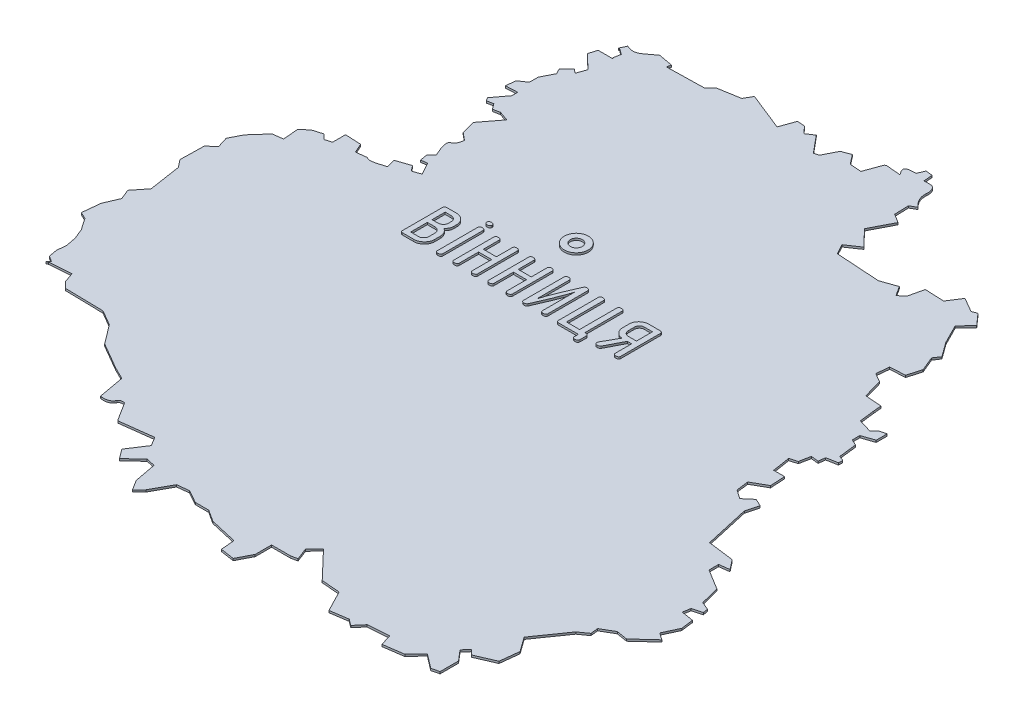
SolidWorks part; units mm, degrees
ref_plane "Спереди" through (0, 0, 0) normal (0, 0, 1) x (1, 0, 0)
ref_plane "Сверху" through (0, 0, 0) normal (0, 1, 0) x (1, 0, 0)
ref_plane "Справа" through (0, 0, 0) normal (1, 0, 0) x (0, 0, -1)
sketch "Эскиз1" plane through (0, 0, 0) normal (0, 1, 0) x (1, 0, 0)
  line B0 (-2034.573, 5821.9238) -> (-2000.1789, 5816.7524)
  line B1 (-2000.1789, 5816.7524) -> (-1981.3651, 5853.0846)
  line B2 (-1981.3651, 5853.0846) -> (-1981.3651, 5893.976)
  line B3 (-1981.3651, 5893.976) -> (-1933.9789, 5893.976)
  line B4 (-1933.9789, 5893.976) -> (-1918.4036, 5897.2145)
  line B5 (-1918.4036, 5897.2145) -> (-1930.0952, 5927.692)
  line B6 (-1930.0952, 5927.692) -> (-1908.0353, 5950.4326)
  line B7 (-1908.0353, 5950.4326) -> (-1841.1927, 5880.3337)
  line B8 (-1841.1927, 5880.3337) -> (-1795.1272, 5876.4576)
  line B9 (-1795.1272, 5876.4576) -> (-1767.8679, 5823.8847)
  line B10 (-1767.8679, 5823.8847) -> (-1723.7253, 5830.3947)
  line B11 (-1723.7253, 5830.3947) -> (-1708.1779, 5818.6955)
  line B12 (-1708.1779, 5818.6955) -> (-1689.3413, 5840.7732)
  line B13 (-1689.3413, 5840.7732) -> (-1636.7862, 5844.6391)
  line B14 (-1636.7862, 5844.6391) -> (-1628.333, 5816.7524)
  line B15 (-1628.333, 5816.7524) -> (-1578.3789, 5823.8847)
  line B16 (-1578.3789, 5823.8847) -> (-1551.1145, 5853.0846)
  line B17 (-1551.1145, 5853.0846) -> (-1515.4123, 5825.8177)
  line B18 (-1515.4123, 5825.8177) -> (-1496.5934, 5830.3947)
  line B19 (-1496.5934, 5830.3947) -> (-1496.5934, 5876.4576)
  line B20 (-1496.5934, 5876.4576) -> (-1518.6787, 5902.4114)
  line B21 (-1518.6787, 5902.4114) -> (-1505.0414, 5917.9968)
  line B22 (-1505.0414, 5917.9968) -> (-1493.36, 5905.6397)
  line B23 (-1493.36, 5905.6397) -> (-1445.3362, 5926.4499)
  line B24 (-1445.3362, 5926.4499) -> (-1440.1444, 5973.7803)
  line B25 (-1440.1444, 5973.7803) -> (-1466.0982, 6010.1302)
  line B26 (-1466.0982, 6010.1302) -> (-1412.8953, 6086.0381)
  line B27 (-1412.8953, 6086.0381) -> (-1390.8456, 6101.6236)
  line B28 (-1390.8456, 6101.6236) -> (-1392.776, 6120.4627)
  line B29 (-1392.776, 6120.4627) -> (-1361.628, 6138.611)
  line B30 (-1361.628, 6138.611) -> (-1334.3788, 6134.067)
  line B31 (-1334.3788, 6134.067) -> (-1288.2956, 6176.2488)
  line B32 (-1288.2956, 6176.2488) -> (-1305.814, 6188.5728)
  line B33 (-1305.814, 6188.5728) -> (-1288.2956, 6226.1928)
  line B34 (-1288.2956, 6226.1928) -> (-1292.2148, 6256.7363)
  line B35 (-1292.2148, 6256.7363) -> (-1322.6948, 6261.9077)
  line B36 (-1322.6948, 6261.9077) -> (-1319.4563, 6280.7393)
  line B37 (-1319.4563, 6280.7393) -> (-1295.4356, 6287.2264)
  line B38 (-1295.4356, 6287.2264) -> (-1297.3736, 6299.5556)
  line B39 (-1297.3736, 6299.5556) -> (-1317.4904, 6307.9782)
  line B40 (-1317.4904, 6307.9782) -> (-1329.8297, 6355.3543)
  line B41 (-1329.8297, 6355.3543) -> (-1380.4392, 6386.5023)
  line B42 (-1380.4392, 6386.5023) -> (-1380.4392, 6410.518)
  line B43 (-1380.4392, 6410.518) -> (-1355.123, 6413.7718)
  line B44 (-1355.123, 6413.7718) -> (-1373.9571, 6437.7722)
  line B45 (-1373.9571, 6437.7722) -> (-1438.8516, 6446.2127)
  line B46 (-1438.8516, 6446.2127) -> (-1464.1601, 6558.468)
  line B47 (-1464.1601, 6558.468) -> (-1455.7096, 6589.6109)
  line B48 (-1455.7096, 6589.6109) -> (-1474.5487, 6598.0767)
  line B49 (-1474.5487, 6598.0767) -> (-1496.5934, 6579.2452)
  line B50 (-1496.5934, 6579.2452) -> (-1518.6787, 6594.8128)
  line B51 (-1518.6787, 6594.8128) -> (-1522.5547, 6625.3131)
  line B52 (-1522.5547, 6625.3131) -> (-1486.215, 6646.0776)
  line B53 (-1486.215, 6646.0776) -> (-1488.1885, 6683.0677)
  line B54 (-1488.1885, 6683.0677) -> (-1515.4123, 6683.0677)
  line B55 (-1515.4123, 6683.0677) -> (-1522.5547, 6727.8377)
  line B56 (-1522.5547, 6727.8377) -> (-1503.741, 6733.0269)
  line B57 (-1503.741, 6733.0269) -> (-1498.5492, 6760.2938)
  line B58 (-1498.5492, 6760.2938) -> (-1479.7303, 6758.3507)
  line B59 (-1479.7303, 6758.3507) -> (-1477.7974, 6775.2189)
  line B60 (-1477.7974, 6775.2189) -> (-1450.533, 6780.4157)
  line B61 (-1450.533, 6780.4157) -> (-1450.533, 6790.8119)
  line B62 (-1450.533, 6790.8119) -> (-1462.8597, 6795.9884)
  line B63 (-1462.8597, 6795.9884) -> (-1468.0438, 6840.126)
  line B64 (-1468.0438, 6840.126) -> (-1482.9942, 6847.2583)
  line B65 (-1482.9942, 6847.2583) -> (-1482.9942, 6866.0874)
  line B66 (-1482.9942, 6866.0874) -> (-1452.4761, 6876.448)
  line B67 (-1452.4761, 6876.448) -> (-1452.4761, 6903.6971)
  line B68 (-1452.4761, 6903.6971) -> (-1468.0438, 6899.8084)
  line B69 (-1468.0438, 6899.8084) -> (-1479.7303, 6888.1269)
  line B70 (-1479.7303, 6888.1269) -> (-1514.1372, 6898.5181)
  line B71 (-1514.1372, 6898.5181) -> (-1518.6787, 6936.1634)
  line B72 (-1518.6787, 6936.1634) -> (-1520.6091, 6956.2675)
  line B73 (-1520.6091, 6956.2675) -> (-1561.5031, 6959.5136)
  line B74 (-1561.5031, 6959.5136) -> (-1575.1251, 7007.5501)
  line B75 (-1575.1251, 7007.5501) -> (-1597.2028, 7019.8717)
  line B76 (-1597.2028, 7019.8717) -> (-1593.9516, 7051.6623)
  line B77 (-1593.9516, 7051.6623) -> (-1556.3113, 7053.613)
  line B78 (-1556.3113, 7053.613) -> (-1546.5704, 7088.0021)
  line B79 (-1546.5704, 7088.0021) -> (-1561.5031, 7123.6992)
  line B80 (-1561.5031, 7123.6992) -> (-1551.1145, 7139.2669)
  line B81 (-1551.1145, 7139.2669) -> (-1577.0657, 7174.9564)
  line B82 (-1577.0657, 7174.9564) -> (-1601.0712, 7222.3401)
  line B83 (-1601.0712, 7222.3401) -> (-1575.1251, 7250.2446)
  line B84 (-1575.1251, 7250.2446) -> (-1599.7936, 7278.1643)
  line B85 (-1599.7936, 7278.1643) -> (-1612.7654, 7273.5973)
  line B86 (-1612.7654, 7273.5973) -> (-1648.4549, 7294.3618)
  line B87 (-1648.4549, 7294.3618) -> (-1669.2093, 7261.9235)
  line B88 (-1669.2093, 7261.9235) -> (-1717.233, 7263.8742)
  line B89 (-1717.233, 7263.8742) -> (-1725.6811, 7227.5294)
  line B90 (-1725.6811, 7227.5294) -> (-1740.601, 7213.9048)
  line B91 (-1740.601, 7213.9048) -> (-1756.1814, 7237.9129)
  line B92 (-1756.1814, 7237.9129) -> (-1795.1272, 7224.2756)
  line B93 (-1795.1272, 7224.2756) -> (-1904.7892, 7231.4283)
  line B94 (-1904.7892, 7231.4283) -> (-1918.4036, 7256.7317)
  line B95 (-1918.4036, 7256.7317) -> (-1885.9602, 7278.7993)
  line B96 (-1885.9602, 7278.7993) -> (-1924.9111, 7319.6907)
  line B97 (-1924.9111, 7319.6907) -> (-1896.3615, 7374.8443)
  line B98 (-1896.3615, 7374.8443) -> (-1918.4036, 7388.4663)
  line B99 (-1918.4036, 7388.4663) -> (-1919.7066, 7424.1635)
  line B100 (-1919.7066, 7424.1635) -> (-1904.7892, 7432.5886)
  line B101 (-1935.2844, 7497.4933) -> (-1954.1109, 7497.4933)
  line B102 (-1954.1109, 7497.4933) -> (-1956.0591, 7519.5582)
  line B103 (-1956.0591, 7519.5582) -> (-1972.9374, 7521.4963)
  line B104 (-1972.9374, 7521.4963) -> (-1980.0646, 7503.9855)
  line B105 (-1980.0646, 7503.9855) -> (-1996.9277, 7502.6774)
  line B106 (-1996.9277, 7480.6048) -> (-2034.573, 7483.8687)
  line B107 (-2034.573, 7483.8687) -> (-2037.809, 7481.9154)
  line B108 (-2037.809, 7481.9154) -> (-2053.3944, 7439.0834)
  line B109 (-2053.3944, 7439.0834) -> (-2081.9593, 7441.0341)
  line B110 (-2081.9593, 7441.0341) -> (-2100.7476, 7465.0321)
  line B111 (-2100.7476, 7465.0321) -> (-2122.8253, 7456.6018)
  line B112 (-2122.8253, 7456.6018) -> (-2140.3615, 7422.2153)
  line B113 (-2140.3615, 7422.2153) -> (-2152.0353, 7418.9692)
  line B114 (-2152.0353, 7418.9692) -> (-2187.7274, 7461.791)
  line B115 (-2187.7274, 7461.791) -> (-2206.5539, 7449.4568)
  line B116 (-2206.5539, 7449.4568) -> (-2222.1215, 7466.9879)
  line B117 (-2222.1215, 7466.9879) -> (-2240.9302, 7468.2833)
  line B118 (-2240.9302, 7468.2833) -> (-2254.57, 7430.6481)
  line B119 (-2254.57, 7430.6481) -> (-2348.6491, 7468.2833)
  line B120 (-2348.6491, 7468.2833) -> (-2360.3407, 7448.1792)
  line B121 (-2360.3407, 7448.1792) -> (-2413.5486, 7439.0834)
  line B122 (-2413.5486, 7439.0834) -> (-2430.4193, 7424.1635)
  line B123 (-2430.4193, 7424.1635) -> (-2522.568, 7422.2153)
  line B124 (-2522.568, 7422.2153) -> (-2520.63, 7432.5886)
  line B125 (-2520.63, 7432.5886) -> (-2556.3271, 7439.0834)
  line B126 (-2616.0247, 7418.9692) -> (-2623.152, 7403.399)
  line B127 (-2623.152, 7403.399) -> (-2622.5195, 7404.6918)
  line B128 (-2622.5195, 7404.6918) -> (-2606.2788, 7393.0027)
  line B129 (-2606.2788, 7393.0027) -> (-2609.5477, 7374.8443)
  line B130 (-2609.5477, 7374.8443) -> (-2606.2788, 7372.8936)
  line B131 (-2606.2788, 7372.8936) -> (-2643.9241, 7372.8936)
  line B132 (-2643.9241, 7372.8936) -> (-2650.4036, 7352.1214)
  line B133 (-2650.4036, 7352.1214) -> (-2614.7192, 7318.3699)
  line B134 (-2614.7192, 7318.3699) -> (-2623.152, 7294.3618)
  line B135 (-2623.152, 7294.3618) -> (-2633.5558, 7302.8099)
  line B136 (-2633.5558, 7302.8099) -> (-2652.3696, 7283.9885)
  line B137 (-2652.3696, 7283.9885) -> (-2645.2297, 7270.3512)
  line B138 (-2645.2297, 7270.3512) -> (-2660.7999, 7239.856)
  line B139 (-2660.7999, 7239.856) -> (-2660.7999, 7217.8037)
  line B140 (-2660.7999, 7217.8037) -> (-2680.9167, 7204.1842)
  line B141 (-2680.9167, 7204.1842) -> (-2682.8547, 7180.166)
  line B142 (-2682.8547, 7180.166) -> (-2653.665, 7181.4665)
  line B143 (-2653.665, 7181.4665) -> (-2653.665, 7166.5109)
  line B144 (-2653.665, 7166.5109) -> (-2679.6187, 7132.1447)
  line B145 (-2679.6187, 7132.1447) -> (-2674.4117, 7123.6992)
  line B146 (-2674.4117, 7123.6992) -> (-2658.8491, 7126.9606)
  line B147 (-2658.8491, 7126.9606) -> (-2648.4707, 7113.3233)
  line B148 (-2648.4707, 7113.3233) -> (-2631.5899, 7116.5593)
  line B149 (-2631.5899, 7116.5593) -> (-2607.5843, 7108.1163)
  line B150 (-2607.5843, 7108.1163) -> (-2643.9241, 7060.753)
  line B151 (-2643.9241, 7060.753) -> (-2634.8233, 7026.3588)
  line B152 (-2634.8233, 7026.3588) -> (-2616.0247, 7010.7886)
  line B153 (-2619.9211, 6944.5886) -> (-2631.5899, 6932.2645)
  line B154 (-2631.5899, 6932.2645) -> (-2628.3564, 6913.4609)
  line B155 (-2628.3564, 6913.4609) -> (-2612.7862, 6915.3989)
  line B156 (-2612.7862, 6915.3989) -> (-2595.9105, 6884.8834)
  line B157 (-2595.9105, 6884.8834) -> (-2616.0247, 6877.7612)
  line B158 (-2616.0247, 6877.7612) -> (-2626.4057, 6891.3807)
  line B159 (-2626.4057, 6891.3807) -> (-2660.7999, 6879.7094)
  line B160 (-2660.7999, 6879.7094) -> (-2655.6106, 6857.6317)
  line B161 (-2699.7406, 6852.4374) -> (-2726.9897, 6849.1913)
  line B162 (-2726.9897, 6849.1913) -> (-2737.3682, 6872.5694)
  line B163 (-2737.3682, 6872.5694) -> (-2776.9642, 6874.5151)
  line B164 (-2776.9642, 6874.5151) -> (-2776.9642, 6842.0691)
  line B165 (-2776.9642, 6842.0691) -> (-2793.8298, 6836.8697)
  line B166 (-2793.8298, 6836.8697) -> (-2805.5087, 6849.1913)
  line B167 (-2805.5087, 6849.1913) -> (-2829.5143, 6842.0691)
  line B168 (-2829.5143, 6842.0691) -> (-2848.3509, 6826.4913)
  line B169 (-2848.3509, 6826.4913) -> (-2845.0921, 6787.5607)
  line B170 (-2845.0921, 6787.5607) -> (-2870.4057, 6784.307)
  line B171 (-2870.4057, 6784.307) -> (-2902.8441, 6747.9596)
  line B172 (-2902.8441, 6747.9596) -> (-2918.4244, 6717.4745)
  line B173 (-2918.4244, 6717.4745) -> (-2909.984, 6690.2076)
  line B174 (-2909.984, 6690.2076) -> (-2928.808, 6673.3445)
  line B175 (-2928.808, 6673.3445) -> (-2930.1161, 6613.6444)
  line B176 (-2930.1161, 6613.6444) -> (-2915.1732, 6594.8128)
  line B177 (-2915.1732, 6594.8128) -> (-2902.8441, 6514.3431)
  line B178 (-2902.8441, 6514.3431) -> (-2928.808, 6481.8971)
  line B179 (-2928.808, 6481.8971) -> (-2918.4244, 6456.5987)
  line B180 (-2918.4244, 6456.5987) -> (-2934.0048, 6420.2437)
  line B181 (-2934.0048, 6420.2437) -> (-2938.5514, 6375.4813)
  line B182 (-2938.5514, 6375.4813) -> (-2921.6629, 6367.7063)
  line B183 (-2921.6629, 6367.7063) -> (-2901.5487, 6338.4786)
  line B184 (-2901.5487, 6338.4786) -> (-2891.1652, 6313.203)
  line B185 (-2891.1652, 6313.203) -> (-2885.9912, 6287.2264)
  line B186 (-2885.9912, 6287.2264) -> (-2887.9343, 6261.9077)
  line B187 (-2887.9343, 6261.9077) -> (-2884.0176, 6241.1559)
  line B188 (-2884.0176, 6241.1559) -> (-2870.4057, 6232.7206)
  line B189 (-2870.4057, 6232.7206) -> (-2876.8853, 6225.601)
  line B190 (-2876.8853, 6225.601) -> (-2872.3539, 6227.5263)
  line B191 (-2872.3539, 6227.5263) -> (-2817.8404, 6231.4074)
  line B192 (-2817.8404, 6231.4074) -> (-2809.4051, 6207.4044)
  line B193 (-2809.4051, 6207.4044) -> (-2793.8298, 6191.824)
  line B194 (-2793.8298, 6191.824) -> (-2698.4325, 6189.8733)
  line B195 (-2698.4325, 6189.8733) -> (-2660.7999, 6167.821)
  line B196 (-2660.7999, 6167.821) -> (-2625.1205, 6120.4627)
  line B197 (-2625.1205, 6120.4627) -> (-2560.2184, 6082.8098)
  line B198 (-2560.2184, 6082.8098) -> (-2529.0729, 6067.2421)
  line B199 (-2442.0982, 5970.524) -> (-2360.3407, 5980.9304)
  line B200 (-2360.3407, 5980.9304) -> (-2346.7085, 5958.8705)
  line B201 (-2346.7085, 5958.8705) -> (-2375.9185, 5914.103)
  line B202 (-2375.9185, 5914.103) -> (-2358.3951, 5890.7477)
  line B203 (-2358.3951, 5890.7477) -> (-2322.7005, 5924.4636)
  line B204 (-2322.7005, 5924.4636) -> (-2300.6456, 5919.2744)
  line B205 (-2300.6456, 5919.2744) -> (-2290.257, 5864.7584)
  line B206 (-2290.257, 5864.7584) -> (-2274.6792, 5839.4498)
  line B207 (-2274.6792, 5839.4498) -> (-2257.806, 5856.3231)
  line B208 (-2257.806, 5856.3231) -> (-2230.5518, 5905.6397)
  line B209 (-2230.5518, 5905.6397) -> (-2201.352, 5908.9036)
  line B210 (-2201.352, 5908.9036) -> (-2168.9009, 5890.7477)
  line B211 (-2168.9009, 5890.7477) -> (-2135.1621, 5890.7477)
  line B212 (-2135.1621, 5890.7477) -> (-2105.9673, 5871.8806)
  line B213 (-2105.9673, 5871.8806) -> (-2037.809, 5856.3231)
  line B214 (-2037.809, 5856.3231) -> (-2034.573, 5821.9238)
  spline B215 degree 2 poles (-1904.7892, 7432.5886) (-1924.9111, 7451.4075) (-1923.603, 7471.5243) knots 0.442982 0.442982 0.442982 0.447368 0.447368 0.447368
  spline B216 degree 2 poles (-1923.603, 7471.5243) (-1921.6548, 7492.2863) (-1935.2844, 7497.4933) knots 0.447368 0.447368 0.447368 0.451754 0.451754 0.451754
  spline B217 degree 2 poles (-1996.9277, 7502.6774) (-2013.7984, 7500.747) (-1996.9277, 7480.6048) knots 0.473684 0.473684 0.473684 0.47807 0.47807 0.47807
  spline B218 degree 2 poles (-2556.3271, 7439.0834) (-2561.5163, 7435.8398) (-2579.0525, 7422.2153) knots 0.565789 0.565789 0.565789 0.570175 0.570175 0.570175
  spline B219 degree 2 poles (-2579.0525, 7422.2153) (-2595.9105, 7408.578) (-2616.0247, 7418.9692) knots 0.570175 0.570175 0.570175 0.574561 0.574561 0.574561
  spline B220 degree 2 poles (-2616.0247, 7010.7886) (-2617.9755, 6991.9596) (-2628.3564, 6988.7313) knots 0.692982 0.692982 0.692982 0.697368 0.697368 0.697368
  spline B221 degree 2 poles (-2628.3564, 6988.7313) (-2638.7349, 6985.4801) (-2619.9211, 6944.5886) knots 0.697368 0.697368 0.697368 0.701754 0.701754 0.701754
  spline B222 degree 2 poles (-2655.6106, 6857.6317) (-2693.2509, 6844.0198) (-2699.7406, 6852.4374) knots 0.736842 0.736842 0.736842 0.741228 0.741228 0.741228
  spline B223 degree 2 poles (-2529.0729, 6067.2421) (-2517.3737, 6004.941) (-2517.3737, 6002.9903) knots 0.907895 0.907895 0.907895 0.912281 0.912281 0.912281
  spline B224 degree 3 poles (-2517.3737, 6002.9903) (-2517.3737, 6001.6771) (-2494.0311, 5997.7833) (-2487.5312, 6013.3865) knots 0.912281 0.912281 0.912281 0.912281 0.916667 0.916667 0.916667 0.916667
  spline B225 degree 3 poles (-2487.5312, 6013.3865) (-2484.9506, 6019.8533) (-2473.9016, 6017.9179) (-2473.2488, 6017.9179) knots 0.916667 0.916667 0.916667 0.916667 0.921053 0.921053 0.921053 0.921053
  spline B226 degree 3 poles (-2473.2488, 6017.9179) (-2471.3057, 6017.9179) (-2444.054, 5970.524) (-2442.0982, 5970.524) knots 0.921053 0.921053 0.921053 0.921053 0.925439 0.925439 0.925439 0.925439
sketch_block_instance "Блок5-1"
sketch_block "Блок5"
extrude "Бобышка-Вытянуть1" add sketch "Эскиз1" along normal blind 5 contours B225 B226 B199 B200 B201 B202 B203 B204 B205 B206 B207 B208 B209 B210 B211 B212 B213 B214 B0 B1 B2 B3 B4 B5 B6 B7 B8 B9 B10 B11 B12 B13 B14 B15 B16 B17 B18 B19 B20 B21 B22 B23 B24 B25 B26 B27 B28 B29 B30 B31 B32 region at (-2113.4527, 0, -6611.8424)
sketch "Эскиз2" plane through (0, 0, 0) normal (0, 1, 0) x (1, 0, 0)
  line L0 (-2500.7494, 6728.2816) -> (-1828.3243, 6728.2816) construction
  circle A0 centre (-2249.0744, 6923.3772) radius 15
  circle A1 centre (-2249.0744, 6923.3772) radius 30
  text T0 "<b>ВІННИЦЯ</b>" font "GOST Type AU" height 110
  point P6 (-2500.7494, 6728.2816)
  dimension "D1" = 30
  dimension "D2" = 60
extrude "Бобышка-Вытянуть2" add sketch "Эскиз2" along normal blind 10
scale "Масштаб1" scale about centroid uniform scaling yes scale factor 0.05
